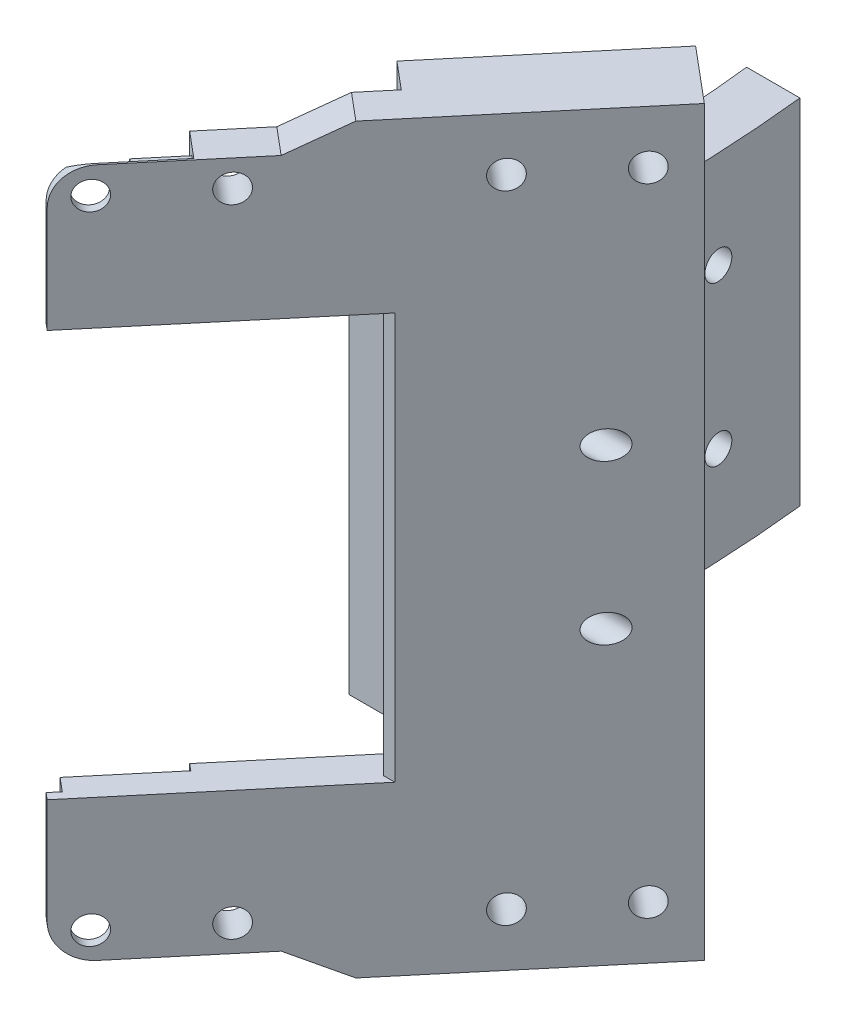
SolidWorks part; units mm, degrees
ref_plane "前视基准面" through (0, 0, 0) normal (0, 0, 1) x (1, 0, 0)
ref_plane "上视基准面" through (0, 0, 0) normal (0, 1, 0) x (1, 0, 0)
ref_plane "右视基准面" through (0, 0, 0) normal (1, 0, 0) x (0, 0, -1)
other "Configuration Table"
sketch3d "3D草图1"
  point P0 (266.2557, 0, 5.9507)
  point P1 (266.2557, 10, 5.9507)
  point P2 (259.8278, 0, 13.6112)
ref_plane "基准面1" through (159.1754, 0, 133.564) normal (0.766, 0, 0.6428) x (0.6428, 0, -0.766)
sketch "草图1" plane through (159.1754, 0, 133.564) normal (0.766, 0, 0.6428) x (0.6428, 0, -0.766)
  line L0 (166.5873, -42) -> (166.5873, 42)
  line L1 (166.5873, 42) -> (138.5873, 42)
  line L2 (138.5873, 42) -> (132.5873, 39)
  line L3 (132.5873, 39) -> (117.7873, 39)
  line L4 (113.7873, 35) -> (113.7873, -35)
  line L5 (117.7873, -39) -> (132.5873, -39)
  line L6 (132.5873, -39) -> (138.5873, -42)
  line L7 (138.5873, -42) -> (166.5873, -42)
  arc A0 (117.7873, 39) -> (113.7873, 35) centre (117.7873, 35) ccw
  arc A1 (113.7873, -35) -> (117.7873, -39) centre (117.7873, -35) ccw
extrude "凸台-拉伸1" add sketch "草图1" against normal blind 1
sketch3d "3D草图2"
  point P0 (266.2557, 0, 5.9507)
  point P1 (266.2557, 10, 5.9507)
  point P2 (259.8278, 0, 13.6112)
ref_plane "基准面2" through (159.1754, 0, 133.564) normal (0.766, 0, 0.6428) x (0.6428, 0, -0.766)
sketch "草图2" plane through (159.1754, 0, 133.564) normal (0.766, 0, 0.6428) x (0.6428, 0, -0.766)
  line L0 (166.5873, -42) -> (166.5873, 42)
  line L1 (166.5873, 42) -> (142.5873, 42)
  line L2 (142.5873, 42) -> (142.5873, -42)
  line L3 (142.5873, -42) -> (166.5873, -42)
extrude "凸台-拉伸2" add sketch "草图2" against normal blind 8
sketch3d "3D草图3"
  point P0 (244.4009, 0, 31.9962)
  point P1 (244.4009, 10, 31.9962)
  point P2 (236.7405, 0, 25.5684)
ref_plane "基准面3" through (85.2255, 0, -101.5678) normal (-0.6428, 0, 0.766) x (0.766, 0, 0.6428)
sketch "草图3" plane through (85.2255, 0, -101.5678) normal (-0.6428, 0, 0.766) x (0.766, 0, 0.6428)
  line L0 (206.7887, -38.2) -> (207.5887, -39)
  line L1 (207.5887, -39) -> (207.5887, -50)
  line L2 (207.5887, -50) -> (197.7887, -50)
  line L3 (197.7887, -50) -> (197.7887, -38.2)
  line L4 (197.7887, -38.2) -> (206.7887, -38.2)
  line L5 (206.7887, 38.2) -> (207.5887, 39)
  line L6 (207.5887, 39) -> (207.5887, 50)
  line L7 (207.5887, 50) -> (197.7887, 50)
  line L8 (197.7887, 50) -> (197.7887, 38.2)
  line L9 (197.7887, 38.2) -> (206.7887, 38.2)
extrude "切除-拉伸1" cut sketch "草图3" along normal blind 30
sketch3d "3D草图4"
  point P0 (266.2557, 0, 5.9507)
  point P1 (266.2557, 10, 5.9507)
  point P2 (259.8278, 0, 13.6112)
ref_plane "基准面4" through (159.1754, 0, 133.564) normal (0.766, 0, 0.6428) x (0.6428, 0, -0.766)
sketch "草图4" plane through (159.1754, 0, 133.564) normal (0.766, 0, 0.6428) x (0.6428, 0, -0.766)
  circle A0 centre (117.2873, -36) radius 1.6
  circle A1 centre (117.2873, 36) radius 1.6
  circle A2 centre (150.6873, 36) radius 1.6
  circle A3 centre (128.6873, 36) radius 1.6
  circle A4 centre (128.6873, -36) radius 1.6
  circle A5 centre (162.0873, 36) radius 1.6
  circle A6 centre (162.0873, -36) radius 1.6
  circle A7 centre (150.6873, -36) radius 1.6
extrude "切除-拉伸2" cut sketch "草图4" against normal blind 12
sketch3d "3D草图5"
  point P0 (0, 0, 25)
  point P1 (10, 0, 25)
  point P2 (0, 10, 25)
ref_plane "基准面5" through (0, 0, 25) normal (0, 0, 1) x (1, 0, 0)
sketch "草图5" plane through (0, 0, 25) normal (0, 0, 1) x (1, 0, 0)
  line L0 (220, -23) -> (280, -23)
  line L1 (280, -23) -> (280, 23)
  line L2 (280, 23) -> (220, 23)
  line L3 (220, 23) -> (220, -23)
extrude "切除-拉伸3" cut sketch "草图5" along normal blind 50
sketch3d "3D草图6"
  point P0 (0, 20, 0)
  point P1 (10, 20, 0)
  point P2 (0, 20, 10)
ref_plane "基准面6" through (0, 20, 0) normal (0, -1, 0) x (-1, 0, 0)
sketch "草图6" plane through (0, 20, 0) normal (0, -1, 0) x (-1, 0, 0)
  line L0 (-249.1238, 22) -> (-243.0866, 22)
  line L1 (-242.0978, -22) -> (-248.1779, -22)
  spline S0 degree 6 poles (-248.1779, -22) (-248.8001, -18.1116) (-249.3071, -14.0548) (-249.6966, -9.8437) (-249.9631, -5.4961) (-250.1, -1.0311) (-250.1, 3.5312) knots 0.698641 0.698641 0.698641 0.698641 0.698641 0.698641 0.698641 1 1 1 1 1 1 1
  spline S1 degree 5 poles (-250.1, 3.5312) (-250.1, 7.3981) (-249.9975, 11.1921) (-249.7978, 14.8992) (-249.5055, 18.5058) (-249.1238, 22) knots 0 0 0 0 0 0 0.212851 0.212851 0.212851 0.212851 0.212851 0.212851
  spline S2 degree 5 poles (-243.0866, 22) (-243.4813, 18.5314) (-243.7849, 14.9338) (-243.993, 11.2231) (-244.1, 7.4164) (-244.1, 3.5312) knots 0.778865 0.778865 0.778865 0.778865 0.778865 0.778865 1 1 1 1 1 1
  spline S3 degree 6 poles (-244.1, 3.5312) (-244.1, -1.0699) (-243.956, -5.5651) (-243.6764, -9.9297) (-243.2689, -14.139) (-242.7411, -18.1695) (-242.0978, -22) knots 0 0 0 0 0 0 0 0.314255 0.314255 0.314255 0.314255 0.314255 0.314255 0.314255
extrude "凸台-拉伸3" add sketch "草图6" along normal blind 40
sketch3d "3D草图7"
  point P0 (0, -18.5, 0)
  point P1 (10, -18.5, 0)
  point P2 (0, -18.5, 10)
ref_plane "基准面7" through (0, -18.5, 0) normal (0, -1, 0) x (-1, 0, 0)
sketch "草图7" plane through (0, -18.5, 0) normal (0, -1, 0) x (-1, 0, 0)
  line L0 (-246, -4) -> (-266, -4)
  line L1 (-266, -4) -> (-250, -23)
  line L2 (-250, -23) -> (-244, -23)
  line L3 (-244, -23) -> (-246, -4)
sketch3d "3D草图8"
  point P0 (0, 12.5, 0)
  point P1 (10, 12.5, 0)
  point P2 (0, 12.5, 10)
ref_plane "基准面8" through (0, 12.5, 0) normal (0, -1, 0) x (-1, 0, 0)
sketch "草图8" plane through (0, 12.5, 0) normal (0, -1, 0) x (-1, 0, 0)
  line L0 (-246, -4) -> (-266, -4)
  line L1 (-266, -4) -> (-250, -23)
  line L2 (-250, -23) -> (-244, -23)
  line L3 (-244, -23) -> (-246, -4)
sketch3d "3D草图9"
  point P0 (285, 0, 0)
  point P1 (285, 10, 0)
  point P2 (285, 0, 10)
ref_plane "基准面9" through (285, 0, 0) normal (1, 0, 0) x (0, 0, -1)
sketch "草图9" plane through (285, 0, 0) normal (1, 0, 0) x (0, 0, -1)
  circle A0 centre (12, -9) radius 1.6
  circle A1 centre (-12, -9) radius 1.6
  circle A2 centre (12, 9) radius 1.6
  circle A3 centre (-12, 9) radius 1.6
extrude "切除-拉伸4" cut sketch "草图9" against normal blind 70
sketch3d "3D草图10"
  point P0 (260, 0, 0)
  point P1 (260, 10, 0)
  point P2 (260, 0, 10)
ref_plane "基准面10" through (260, 0, 0) normal (1, 0, 0) x (0, 0, -1)
sketch "草图10" plane through (260, 0, 0) normal (1, 0, 0) x (0, 0, -1)
  circle A0 centre (12, -9) radius 3.25
  circle A1 centre (-12, -9) radius 3.25
  circle A2 centre (12, 9) radius 3.25
  circle A3 centre (-12, 9) radius 3.25
sketch3d "3D草图11"
  point P0 (275, 0, 0)
  point P1 (275, 10, 0)
  point P2 (275, 0, 10)
ref_plane "基准面11" through (275, 0, 0) normal (1, 0, 0) x (0, 0, -1)
sketch "草图11" plane through (275, 0, 0) normal (1, 0, 0) x (0, 0, -1)
  circle A0 centre (-12, -9) radius 4
  circle A1 centre (-12, 9) radius 4
sketch3d "3D草图12"
  point P0 (266.2557, -30, 5.9507)
  point P1 (259.8278, -30, 13.6112)
  point P2 (258.5952, -30, -0.4772)
ref_plane "基准面12" through (0, -30, 0) normal (0, -1, 0) x (-1, 0, 0)
sketch "草图12" plane through (0, -30, 0) normal (0, -1, 0) x (-1, 0, 0)
  line L0 (-251.7313, -22.4823) -> (-233.0905, -44.6976)
  line L1 (-233.0905, -44.6976) -> (-231.1754, -43.0906)
  line L2 (-231.1754, -43.0906) -> (-245.986, -17.6614)
  line L3 (-245.986, -17.6614) -> (-251.7313, -22.4823)
sketch3d "3D草图13"
  point P0 (266.2557, 26, 5.9507)
  point P1 (259.8278, 26, 13.6112)
  point P2 (258.5952, 26, -0.4772)
ref_plane "基准面13" through (0, 26, 0) normal (0, -1, 0) x (-1, 0, 0)
sketch "草图13" plane through (0, 26, 0) normal (0, -1, 0) x (-1, 0, 0)
  line L0 (-251.7313, -22.4823) -> (-233.0905, -44.6976)
  line L1 (-233.0905, -44.6976) -> (-231.1754, -43.0906)
  line L2 (-231.1754, -43.0906) -> (-245.986, -17.6614)
  line L3 (-245.986, -17.6614) -> (-251.7313, -22.4823)
sketch3d "3D草图14"
  point P0 (266.2557, 0, 5.9507)
  point P1 (266.2557, 10, 5.9507)
  point P2 (259.8278, 0, 13.6112)
ref_plane "基准面14" through (159.1754, 0, 133.564) normal (0.766, 0, 0.6428) x (0.6428, 0, -0.766)
sketch "草图14" plane through (159.1754, 0, 133.564) normal (0.766, 0, 0.6428) x (0.6428, 0, -0.766)
  line L0 (125.0873, -34) -> (125.0873, -26)
  line L1 (125.0873, -26) -> (122.0873, -26)
  line L2 (122.0873, -26) -> (122.0873, -34)
  line L3 (122.0873, -34) -> (125.0873, -34)
  line L4 (125.0873, 26) -> (125.0873, 34)
  line L5 (125.0873, 34) -> (122.0873, 34)
  line L6 (122.0873, 34) -> (122.0873, 26)
  line L7 (122.0873, 26) -> (125.0873, 26)
sketch3d "3D草图15"
  point P0 (266.2557, -18.5, 5.9507)
  point P1 (259.8278, -18.5, 13.6112)
  point P2 (258.5952, -18.5, -0.4772)
ref_plane "基准面15" through (0, -18.5, 0) normal (0, -1, 0) x (-1, 0, 0)
sketch "草图15" plane through (0, -18.5, 0) normal (0, -1, 0) x (-1, 0, 0)
  line L0 (-265.4896, -5.3079) -> (-250.0627, -23.693)
  line L1 (-250.0627, -23.693) -> (-245.5195, -4.2159)
  line L2 (-245.5195, -4.2159) -> (-265.4896, -5.3079)
extrude "凸台-拉伸8" add sketch "草图15" against normal blind 6
sketch3d "3D草图16"
  point P0 (266.2557, 12.5, 5.9507)
  point P1 (259.8278, 12.5, 13.6112)
  point P2 (258.5952, 12.5, -0.4772)
ref_plane "基准面16" through (0, 12.5, 0) normal (0, -1, 0) x (-1, 0, 0)
sketch "草图16" plane through (0, 12.5, 0) normal (0, -1, 0) x (-1, 0, 0)
  line L0 (-265.4896, -5.3079) -> (-250.0627, -23.693)
  line L1 (-250.0627, -23.693) -> (-245.5195, -4.2159)
  line L2 (-245.5195, -4.2159) -> (-265.4896, -5.3079)
extrude "凸台-拉伸9" add sketch "草图16" against normal blind 6
sketch3d "3D草图17"
  point P0 (266.2557, 0, 5.9507)
  point P1 (266.2557, 10, 5.9507)
  point P2 (259.8278, 0, 13.6112)
ref_plane "基准面17" through (159.1754, 0, 133.564) normal (0.766, 0, 0.6428) x (0.6428, 0, -0.766)
sketch "草图17" plane through (159.1754, 0, 133.564) normal (0.766, 0, 0.6428) x (0.6428, 0, -0.766)
  line L0 (143.5873, 23) -> (143.5873, 39)
  line L1 (143.5873, 39) -> (125.5873, 39)
  line L2 (125.5873, 39) -> (125.5873, 23)
  line L3 (125.5873, 23) -> (143.5873, 23)
  line L4 (143.5873, -39) -> (143.5873, -23)
  line L5 (143.5873, -23) -> (125.5873, -23)
  line L6 (125.5873, -23) -> (125.5873, -39)
  line L7 (125.5873, -39) -> (143.5873, -39)
sketch3d "3D草图18"
  point P0 (266.2557, 0, 5.9507)
  point P1 (266.2557, 10, 5.9507)
  point P2 (259.8278, 0, 13.6112)
ref_plane "基准面18" through (159.1754, 0, 133.564) normal (0.766, 0, 0.6428) x (0.6428, 0, -0.766)
sketch "草图18" plane through (159.1754, 0, 133.564) normal (0.766, 0, 0.6428) x (0.6428, 0, -0.766)
  line L0 (125.5873, 23) -> (125.5873, 32)
  line L1 (125.5873, 32) -> (115.0873, 32)
  line L2 (115.0873, 32) -> (115.0873, 23)
  line L3 (115.0873, 23) -> (125.5873, 23)
  line L4 (125.5873, -32) -> (125.5873, -23)
  line L5 (125.5873, -23) -> (115.0873, -23)
  line L6 (115.0873, -23) -> (115.0873, -32)
  line L7 (115.0873, -32) -> (125.5873, -32)
extrude "凸台-拉伸11" add sketch "草图18" against normal blind 3
sketch3d "3D草图19"
  point P0 (266.2557, 0, 5.9507)
  point P1 (266.2557, 10, 5.9507)
  point P2 (259.8278, 0, 13.6112)
ref_plane "基准面19" through (159.1754, 0, 133.564) normal (0.766, 0, 0.6428) x (0.6428, 0, -0.766)
sketch "草图19" plane through (159.1754, 0, 133.564) normal (0.766, 0, 0.6428) x (0.6428, 0, -0.766)
  line L0 (125.5873, 32) -> (125.5873, 38)
  line L1 (125.5873, 38) -> (118.5873, 38)
  line L2 (118.5873, 38) -> (118.5873, 32)
  line L3 (118.5873, 32) -> (125.5873, 32)
  line L4 (125.5873, -38) -> (125.5873, -32)
  line L5 (125.5873, -32) -> (118.5873, -32)
  line L6 (118.5873, -32) -> (118.5873, -38)
  line L7 (118.5873, -38) -> (125.5873, -38)
sketch3d "3D草图20"
  point P0 (266.2557, 0, 5.9507)
  point P1 (266.2557, 10, 5.9507)
  point P2 (259.8278, 0, 13.6112)
ref_plane "基准面20" through (159.1754, 0, 133.564) normal (0.766, 0, 0.6428) x (0.6428, 0, -0.766)
sketch "草图20" plane through (159.1754, 0, 133.564) normal (0.766, 0, 0.6428) x (0.6428, 0, -0.766)
  circle A0 centre (162.0873, -36) radius 1.6
  circle A1 centre (150.6873, -36) radius 1.6
  circle A2 centre (128.6873, -36) radius 1.6
  circle A3 centre (117.2873, -36) radius 1.6
  circle A4 centre (162.0873, 36) radius 1.6
  circle A5 centre (150.6873, 36) radius 1.6
  circle A6 centre (128.6873, 36) radius 1.6
  circle A7 centre (117.2873, 36) radius 1.6
sketch3d "3D草图21"
  point P0 (266.2557, 0, 5.9507)
  point P1 (266.2557, 10, 5.9507)
  point P2 (259.8278, 0, 13.6112)
ref_plane "基准面21" through (159.1754, 0, 133.564) normal (0.766, 0, 0.6428) x (0.6428, 0, -0.766)
sketch "草图21" plane through (159.1754, 0, 133.564) normal (0.766, 0, 0.6428) x (0.6428, 0, -0.766)
  line L0 (125.5873, 32) -> (125.5873, 38)
  line L1 (125.5873, 38) -> (120.5873, 38)
  line L2 (120.5873, 38) -> (120.5873, 32)
  line L3 (120.5873, 32) -> (125.5873, 32)
  line L4 (125.5873, -38) -> (125.5873, -32)
  line L5 (125.5873, -32) -> (120.5873, -32)
  line L6 (120.5873, -32) -> (120.5873, -38)
  line L7 (120.5873, -38) -> (125.5873, -38)
extrude "凸台-拉伸13" add sketch "草图21" against normal blind 2
sketch3d "3D草图22"
  point P0 (266.2557, 0, 5.9507)
  point P1 (266.2557, 10, 5.9507)
  point P2 (259.8278, 0, 13.6112)
ref_plane "基准面22" through (159.1754, 0, 133.564) normal (0.766, 0, 0.6428) x (0.6428, 0, -0.766)
sketch "草图22" plane through (159.1754, 0, 133.564) normal (0.766, 0, 0.6428) x (0.6428, 0, -0.766)
  circle A0 centre (162.0873, -36) radius 1.6
  circle A1 centre (150.6873, -36) radius 1.6
  circle A2 centre (128.6873, -36) radius 1.6
  circle A3 centre (117.2873, -36) radius 1.6
  circle A4 centre (162.0873, 36) radius 1.6
  circle A5 centre (150.6873, 36) radius 1.6
  circle A6 centre (128.6873, 36) radius 1.6
  circle A7 centre (117.2873, 36) radius 1.6
sketch3d "3D草图23"
  point P0 (266.2557, 0, 5.9507)
  point P1 (266.2557, 10, 5.9507)
  point P2 (259.8278, 0, 13.6112)
ref_plane "基准面23" through (159.1754, 0, 133.564) normal (0.766, 0, 0.6428) x (0.6428, 0, -0.766)
sketch "草图23" plane through (159.1754, 0, 133.564) normal (0.766, 0, 0.6428) x (0.6428, 0, -0.766)
  line L0 (143.5873, -23) -> (143.5873, -42)
  line L1 (143.5873, -42) -> (138.5873, -42)
  line L2 (138.5873, -42) -> (132.5873, -39)
  line L3 (132.5873, -39) -> (125.5873, -39)
  line L4 (125.5873, -39) -> (125.5873, -23)
  line L5 (125.5873, -23) -> (143.5873, -23)
  line L6 (143.5873, 23) -> (143.5873, 42)
  line L7 (143.5873, 42) -> (138.5873, 42)
  line L8 (138.5873, 42) -> (132.5873, 39)
  line L9 (132.5873, 39) -> (125.5873, 39)
  line L10 (125.5873, 39) -> (125.5873, 23)
  line L11 (125.5873, 23) -> (143.5873, 23)
extrude "凸台-拉伸14" add sketch "草图23" against normal blind 4
sketch3d "3D草图24"
  point P0 (266.2557, 0, 5.9507)
  point P1 (266.2557, 10, 5.9507)
  point P2 (259.8278, 0, 13.6112)
ref_plane "基准面24" through (159.1754, 0, 133.564) normal (0.766, 0, 0.6428) x (0.6428, 0, -0.766)
sketch "草图24" plane through (159.1754, 0, 133.564) normal (0.766, 0, 0.6428) x (0.6428, 0, -0.766)
  circle A0 centre (162.0873, -36) radius 1.6
  circle A1 centre (150.6873, -36) radius 1.6
  circle A2 centre (128.6873, -36) radius 1.6
  circle A3 centre (117.2873, -36) radius 1.6
  circle A4 centre (162.0873, 36) radius 1.6
  circle A5 centre (150.6873, 36) radius 1.6
  circle A6 centre (128.6873, 36) radius 1.6
  circle A7 centre (117.2873, 36) radius 1.6
extrude "切除-拉伸7" cut sketch "草图24" against normal blind 12
